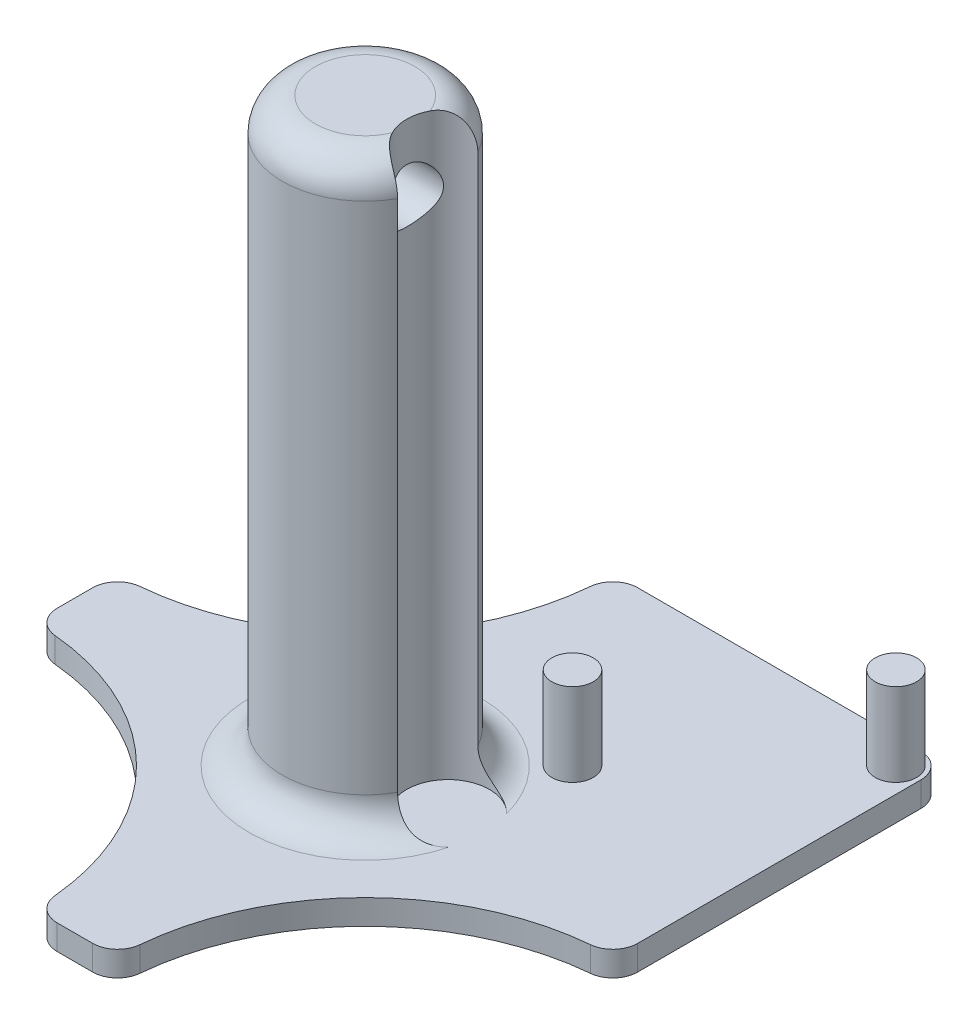
SolidWorks part; units mm, degrees
ref_plane "Front Plane" through (0, 0, 0) normal (0, 0, 1) x (1, 0, 0)
ref_plane "Top Plane" through (0, 0, 0) normal (0, 1, 0) x (1, 0, 0)
ref_plane "Right Plane" through (0, 0, 0) normal (1, 0, 0) x (0, 0, -1)
sketch "Sketch1" plane through (0, 0, 0) normal (0, 1, 0) x (1, 0, 0)
  line L1 (0, 0) -> (70, 0)
  line L2 (0, 0) -> (0, 70)
  line L3 (0, 70) -> (70, 70)
  line L4 (70, 0) -> (70, 70)
  circle A0 centre (0, 70) radius 30
  circle A1 centre (0, 0) radius 30
  circle A2 centre (70, 0) radius 30
  circle A3 centre (70, 70) radius 30
extrude "Boss-Extrude1" add sketch "Sketch1" along normal blind 3 contours A3 L3 A0 L2 A1 L1 A2 L4 region at (35, 0, -35)
fillet "Fillet1" radius 3 8 edges at (70, 1.5, -30) (70, 1.5, -40) (40, 1.5, -70) (30, 1.5, -70) (0, 1.5, -40) (0, 1.5, -30) (30, 1.5, 0) (40, 1.5, 0)
sketch "Sketch2" plane through (0, 3, 0) normal (0, 1, 0) x (1, 0, 0)
  line L0 (0, 35) -> (70, 35)
  line L1 (0, 32.8634) -> (0, 37.1366) construction
  line L2 (70, 32.8634) -> (70, 37.1366) construction
  circle A0 centre (35, 35) radius 10
extrude "Boss-Extrude3" add sketch "Sketch2" along normal blind 70 contours A0
sketch "Sketch4" plane through (70, 0, 0) normal (1, 0, 0) x (0, 0, -1)
  line L0 (35, 3) -> (35, 73)
  line L1 (32.8634, 3) -> (37.1366, 3) construction
  line L2 (45, 73) -> (25, 73) construction
  circle A0 centre (35, 65) radius 2.5
extrude "Cut-Extrude2" cut sketch "Sketch4" against normal blind 70 contours A0
sketch "Sketch7" plane through (70, 0, 0) normal (1, 0, 0) x (0, 0, -1)
  circle A0 centre (35, 65) radius 3.25
extrude "Cut-Extrude3" cut sketch "Sketch7" against normal blind 38
fillet "Fillet3" radius 4 1 edges at (35, 73, -25)
sketch "Sketch8" plane through (0, 73, 0) normal (0, 1, 0) x (1, 0, 0)
  circle A0 centre (45, 35) radius 5
  circle A1 centre (35, 35) radius 10 construction
extrude "Cut-Extrude4" cut sketch "Sketch8" against normal blind 70
sketch "Sketch10" plane through (0, 3, 0) normal (0, 1, 0) x (1, 0, 0)
  line L0 (70, 32.8634) -> (70, 37.1366) construction
  line L1 (70, 35) -> (35, 35)
  line L2 (70, 35) -> (70, 70)
  line L3 (70, 70) -> (35, 70)
  line L4 (35, 35) -> (35, 70)
  line L5 (32.8634, 70) -> (37.1366, 70) construction
extrude "Boss-Extrude5" add sketch "Sketch10" against normal blind 3
fillet "Fillet5" radius 3 1 edges at (70, 1.5, -70)
sketch "Sketch11" plane through (0, 3, 0) normal (0, 1, 0) x (1, 0, 0)
  circle A0 centre (67, 67) radius 2.5
  circle A1 centre (47.5, 47.5) radius 2.5
extrude "Boss-Extrude6" add sketch "Sketch11" along normal blind 10
fillet "Fillet6" radius 4 1 edges at (25, 3, -35)
